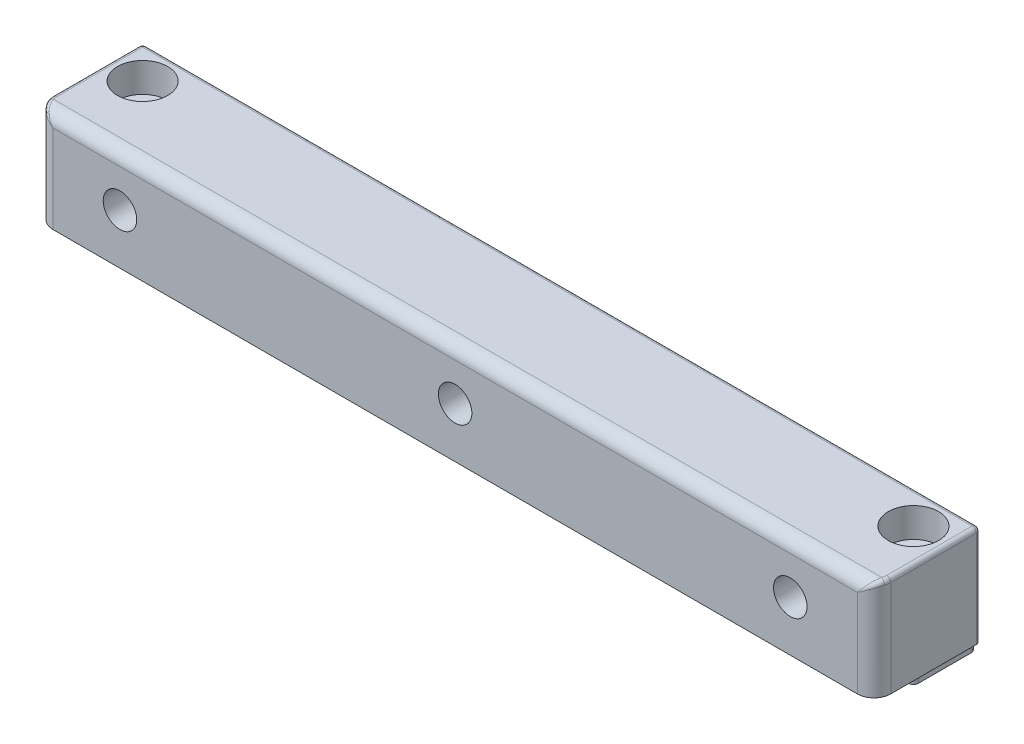
SolidWorks part; units mm, degrees
material "ABS"
ref_plane "Front Plane" through (0, 0, 0) normal (0, 0, 1) x (1, 0, 0)
ref_plane "Top Plane" through (0, 0, 0) normal (0, 1, 0) x (1, 0, 0)
ref_plane "Right Plane" through (0, 0, 0) normal (1, 0, 0) x (0, 0, -1)
sketch "Sketch1" plane through (0, 0, 0) normal (0, 1, 0) x (1, 0, 0)
  line L0 (0, 0) -> (0, 4) construction
  line L1 (-50, -8.7) -> (50, -8.7)
  line L2 (-50, -8.7) -> (-50, 4)
  line L3 (-50, 4) -> (50, 4)
  line L4 (50, -8.7) -> (50, 4)
  line L5 (-50, -8.7) -> (50, 4) construction
  line L6 (-50, 4) -> (50, -8.7) construction
  line L7 (0, 0) -> (50, 0) construction
  circle A0 centre (46, 0) radius 1.75
  circle A1 centre (-46, 0) radius 1.75
  point P0 (0, -2.35)
  dimension "D4" = 92
  dimension "D5" = 3.5
  dimension "D1" = 100
  dimension "D2" = 4
  dimension "D3" = 8.7
extrude "Boss-Extrude1" add sketch "Sketch1" along normal blind 12
sketch "Sketch2" plane through (0, 12, 0) normal (0, 1, 0) x (1, 0, 0)
  circle A0 centre (46, 0) radius 3
  circle A1 centre (-46, 0) radius 3
  dimension "D1" = 6
extrude "Cut-Extrude1" cut sketch "Sketch2" against normal blind 3.5
sketch "Sketch3" plane through (0, 0, 8.7) normal (0, 0, 1) x (1, 0, 0)
  line L0 (50, 6) -> (-50, 6) construction
  line L3 (0, 6) -> (0, 0) construction
  line L4 (-50, 0) -> (50, 0) construction
  circle A0 centre (40, 6) radius 1.6
  circle A1 centre (0, 6) radius 1.6
  circle A2 centre (-40, 6) radius 1.6
  dimension "D1" = 3.2
  dimension "D2" = 80
  dimension "D3" = 6
extrude "Cut-Extrude2" cut sketch "Sketch3" against normal blind 50
sketch "Sketch4" plane through (0, 0, 8.7) normal (0, 0, -1) x (-1, 0, 0)
  circle A0 centre (40, 6) radius 2
  circle A1 centre (0, 6) radius 2
  circle A2 centre (-40, 6) radius 2
  dimension "D1" = 4
extrude "Cut-Extrude3" cut sketch "Sketch4" along normal blind 7
fillet "Fillet1" radius 2 2 edges at (50, 6, 8.7) (-50, 6, 8.7)
fillet "Fillet2" radius 1.5 1 edges at (0, 12, 8.7)
sketch "Sketch5" plane through (0, 0, 0) normal (0, -1, 0) x (1, 0, 0)
  line L1 (-42.25, 3.75) -> (-49.75, 3.75)
  line L2 (-42.25, 3.75) -> (-42.25, -3.75)
  line L3 (-42.25, -3.75) -> (-49.75, -3.75)
  line L4 (-49.75, 3.75) -> (-49.75, -3.75)
  line L5 (-42.25, 3.75) -> (-49.75, -3.75) construction
  line L6 (-42.25, -3.75) -> (-49.75, 3.75) construction
  line L7 (0, 0) -> (0, -4) construction
  line L8 (50, -4) -> (-50, -4) construction
  line L9 (42.25, -3.75) -> (49.75, -3.75)
  line L10 (49.75, 3.75) -> (49.75, -3.75)
  line L11 (42.25, 3.75) -> (49.75, 3.75)
  line L12 (42.25, 3.75) -> (42.25, -3.75)
  circle A0 centre (-46, 0) radius 1.75 construction
  circle A1 centre (-46, 0) radius 1.75
  circle A2 centre (46, 0) radius 1.75
  point P0 (-46, 0)
  dimension "D1" = 7.5
extrude "Boss-Extrude2" add sketch "Sketch5" along normal blind 0.8
fillet "Fillet3" radius 0.6 8 edges at (49.75, -0.4, -3.75) (49.75, -0.4, 3.75) (42.25, -0.4, 3.75) (42.25, -0.4, -3.75) (-42.25, -0.4, -3.75) (-42.25, -0.4, 3.75) (-49.75, -0.4, -3.75) (-49.75, -0.4, 3.75)
fillet "Fillet4" radius 0.5 9 edges at (-49.5015, 11.7553, 8.0212) (-49.9841, 12, 6.952) (49.5015, 11.7553, 8.0212) (49.9841, 12, 6.952) (-50, 12, 1.35) (0, 12, -4) (50, 12, 1.35) (50, 6, -4) (-50, 6, -4)
